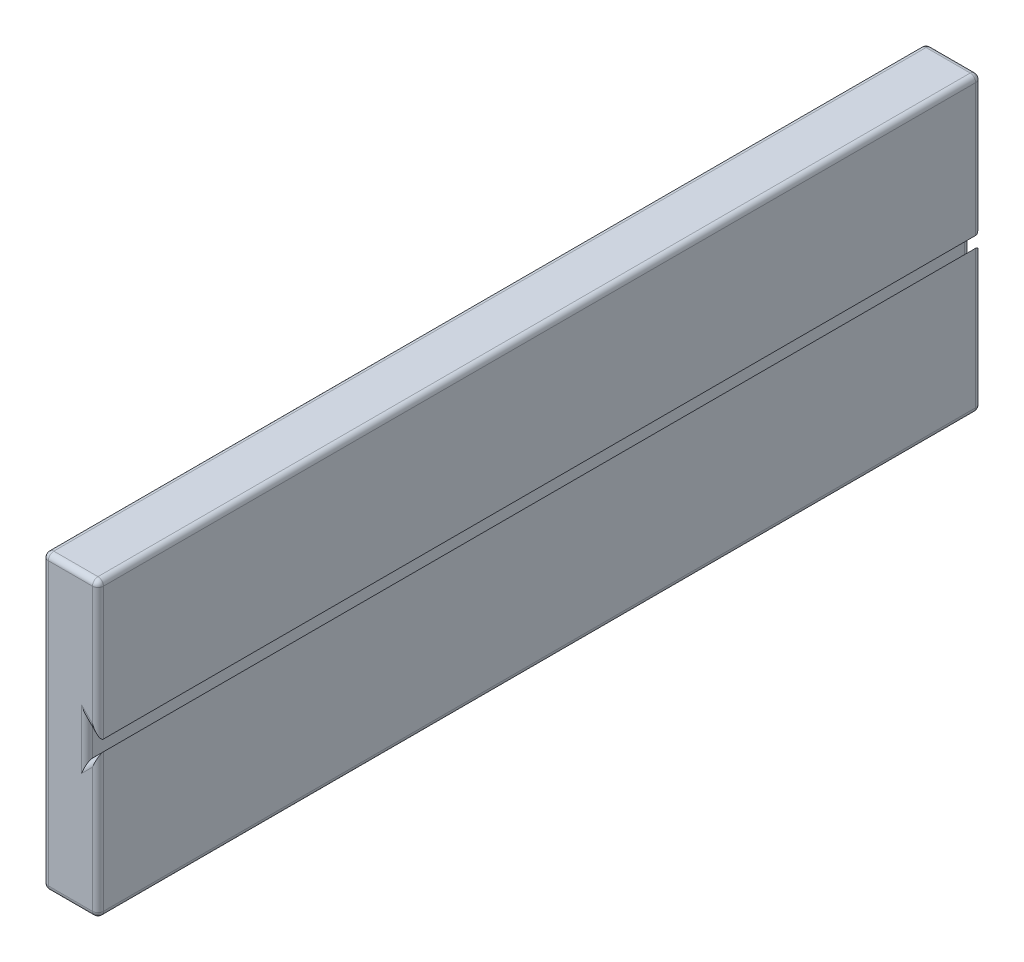
SolidWorks part; units mm, degrees
ref_plane "Front Plane" through (0, 0, 0) normal (0, 0, 1) x (1, 0, 0)
ref_plane "Top Plane" through (0, 0, 0) normal (0, 1, 0) x (1, 0, 0)
ref_plane "Right Plane" through (0, 0, 0) normal (1, 0, 0) x (0, 0, -1)
sketch "Sketch1" plane through (0, 0, 0) normal (1, 0, 0) x (0, 0, -1)
  line L1 (0, 0) -> (160, 0)
  line L2 (0, 0) -> (0, 53)
  line L3 (0, 53) -> (160, 53)
  line L4 (160, 0) -> (160, 53)
  dimension "D1" = 53
  dimension "D2" = 160
extrude "Boss-Extrude1" add sketch "Sketch1" along normal blind 10
sketch "Sketch2" plane through (0, 0, 0) normal (0, 0, 1) x (1, 0, 0)
  line L0 (0, 27.0254) -> (10, 27.0254) construction
  line L1 (0, 53) -> (0, 0) construction
  line L2 (10, 53) -> (10, 0) construction
sketch "Sketch4" plane through (0, 0, 0) normal (0, 0, 1) x (1, 0, 0)
  line L0 (10, 26.0254) -> (8, 24.0254)
  line L1 (10, 53) -> (10, 0) construction
  line L2 (8, 24.0254) -> (8, 30.0254)
  line L3 (8, 30.0254) -> (10, 28.0254)
  line L4 (0, 27.0254) -> (10, 27.0254) construction
  dimension "D1" = 1
  dimension "D2" = 1
  dimension "D3" = 3
  dimension "D4" = 3
  dimension "D5" = 2
extrude "Cut-Extrude2" cut sketch "Sketch4" against normal through all and the other way through all flip side to cut
fillet "Fillet1" radius 1 20 edges at (10, 0, -80) (0, 0, -80) (9, 29.0254, -160) (10, 40.5127, -160) (0, 26.5, -160) (5, 0, -160) (10, 13.0127, -160) (9, 25.0254, -160) (8, 27.0254, -160) (5, 0, 0) (0, 26.5, 0) (10, 40.5127, 0) (9, 29.0254, 0) (8, 27.0254, 0) (9, 25.0254, 0) (10, 13.0127, 0) (5, 53, -160) (10, 53, -80) (5, 53, 0) (0, 53, -80)
sketch "Sketch5" plane through (0, 53, 0) normal (0, 1, 0) x (1, 0, 0)
  line L0 (1, 80) -> (9, 80) construction
  line L1 (1, 159) -> (1, 1) construction
  line L2 (9, 1) -> (9, 159) construction
